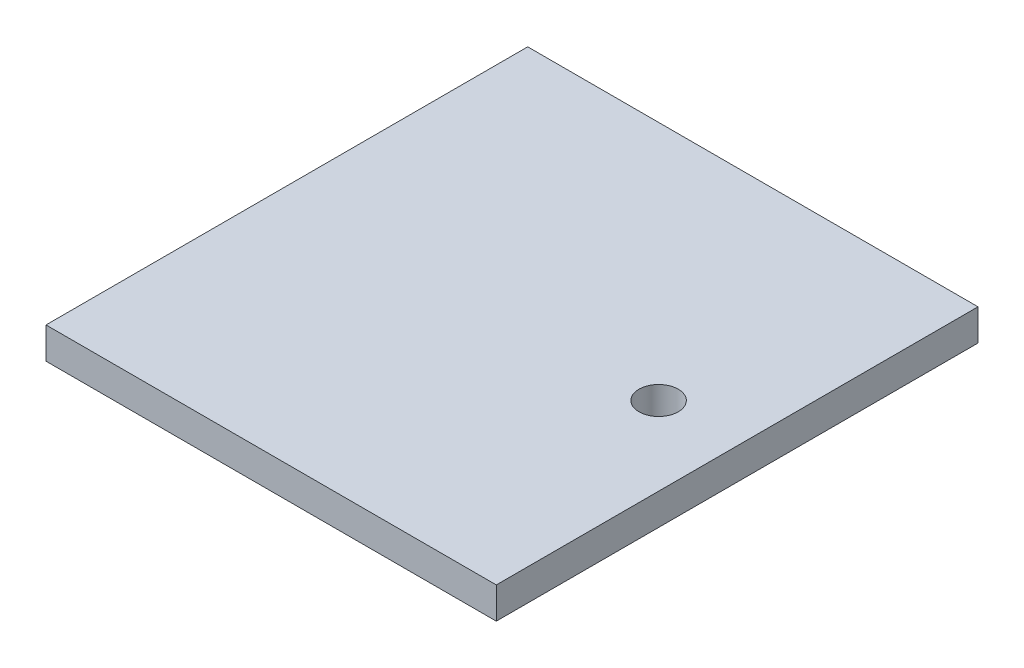
SolidWorks part; units mm, degrees
material "Maple"
ref_plane "Front Plane" through (0, 0, 0) normal (0, 0, 1) x (1, 0, 0)
ref_plane "Top Plane" through (0, 0, 0) normal (0, 1, 0) x (1, 0, 0)
ref_plane "Right Plane" through (0, 0, 0) normal (1, 0, 0) x (0, 0, -1)
sketch "Sketch1" plane through (0, 0, 0) normal (0, 1, 0) x (1, 0, 0)
  line L0 (86, -181.1) -> (86, 120.4) construction
  line L1 (0, 0) -> (86, 0)
  line L2 (0, 0) -> (0, 92)
  line L3 (0, 92) -> (86, 92)
  line L4 (86, 0) -> (86, 92)
  dimension "D2" = 92
extrude "Boss-Extrude1" add sketch "Sketch1" along normal blind 6
ref_plane "Plane1" through (0, 3, 0) normal (0, 1, 0) x (1, 0, 0)
hole_wizard "Ø7.5 (7.5) Diameter Hole1" positions "Sketch3" profile "Sketch2" hole size "Ø7.5" standard "ANSI Metric" end condition through all
sketch "Sketch3" plane through (0, 6, 0) normal (0, 1, 0) x (1, 0, 0)
  circle A0 centre (71, 46) radius 4 construction
  point P0 (71, 46)
sketch "Sketch2" plane through (71, 6, -46) normal (1, 0, 0) x (0, 0, 1)
  line L0 (0, 0) -> (0, 6)
  line L1 (0, 6) -> (3.75, 6)
  line L2 (3.75, 6) -> (3.75, 0)
  line L5 (3.75, 0) -> (0, 0)
  line L11 (0, -6.35) -> (0, 107.95) construction
  dimension "Thru Hole Dia." = 7.5
  dimension "Thru Hole Depth" = 6
